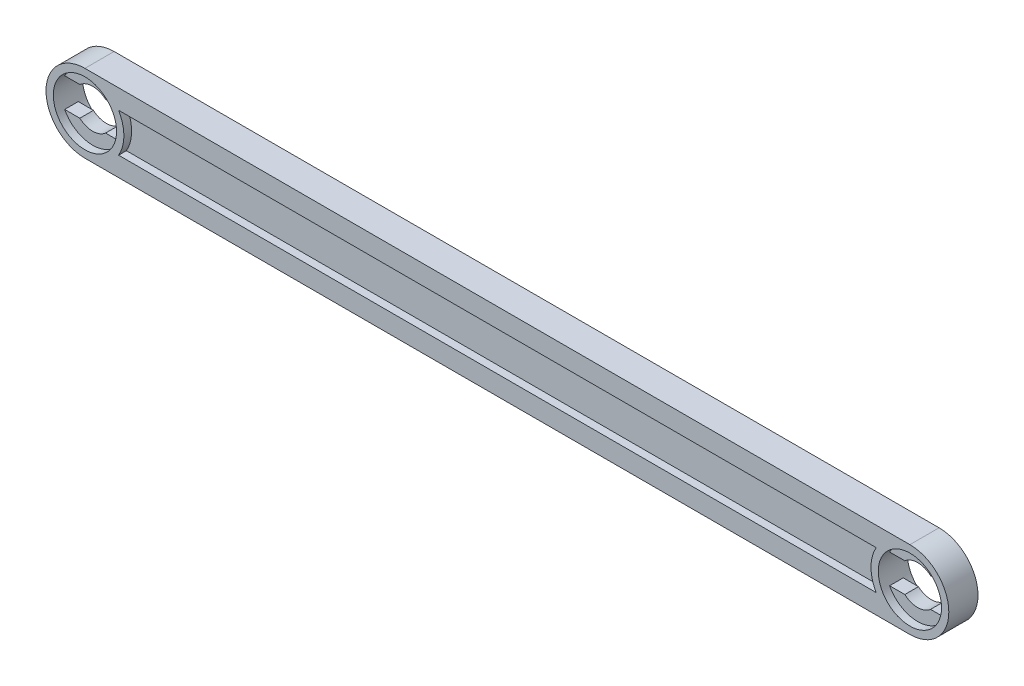
SolidWorks part; units mm, degrees
ref_plane "前视基准面" through (0, 0, 0) normal (0, 0, 1) x (1, 0, 0)
ref_plane "上视基准面" through (0, 0, 0) normal (0, 1, 0) x (1, 0, 0)
ref_plane "右视基准面" through (0, 0, 0) normal (1, 0, 0) x (0, 0, -1)
sketch "草图1" plane through (0, 0, 0) normal (0, 0, 1) x (1, 0, 0)
  line L1 (0, 4) -> (84.8, 4)
  line L3 (0, -4) -> (84.8, -4)
  arc A0 (0, 4) -> (0, -4) centre (0, 0) ccw
  arc A1 (84.8, -4) -> (84.8, 4) centre (84.8, 0) ccw
  dimension "D1" = 84.8
  dimension "D2" = 4
  dimension "D4" = 4
  dimension "D3" = 84.8
extrude "凸台-拉伸1" add sketch "草图1" against normal blind 3
sketch "草图2" plane through (0, 0, 0) normal (0, 0, 1) x (1, 0, 0)
  line L0 (1.3229, -1.5) -> (2.8831, -1.5)
  line L1 (-2.8831, -1.5) -> (-1.3229, -1.5)
  line L2 (1.3229, 1.5) -> (2.8831, 1.5)
  line L3 (-2.8831, 1.5) -> (-1.3229, 1.5)
  arc A0 (1.3229, 1.5) -> (-1.3229, 1.5) centre (0, 0) ccw
  arc A1 (-2.8831, 1.5) -> (-2.8831, -1.5) centre (0, 0) ccw
  arc A3 (2.8831, -1.5) -> (2.8831, 1.5) centre (0, 0) ccw
  arc A4 (-1.3229, -1.5) -> (1.3229, -1.5) centre (0, 0) ccw
extrude "切除-拉伸1" cut sketch "草图2" against normal up to next
sketch "草图3" plane through (0, 0, 0) normal (0, 0, 1) x (1, 0, 0)
  circle A1 centre (0, 0) radius 3.25
extrude "切除-拉伸2" cut sketch "草图3" against normal blind 0.8
extrude "切除-拉伸3" cut sketch "草图3<2>" along normal blind 0.8 from offset 3 offset against normal yes
sketch "草图3<2>" plane through (0, 0, 0) normal (0, 0, 1) x (1, 0, 0) same geometry as "草图3"
pattern_linear "阵列(线性)1" count 2 spacing 84.8 along (1, 0, 0) of "切除-拉伸1", "切除-拉伸2", "切除-拉伸3"
sketch "草图4" plane through (0, 0, 0) normal (0, 0, 1) x (1, 0, 0)
  line L0 (0, 0) -> (0, 2) construction
  line L1 (0, 0) -> (0, -2) construction
  line L2 (0, 2) -> (3.4641, 2) construction
  line L3 (0, -2) -> (3.4641, -2) construction
  line L4 (84.8, 0) -> (84.8, 2) construction
  line L5 (84.8, 2) -> (81.3359, 2) construction
  line L6 (84.8, 0) -> (84.8, -2) construction
  line L7 (84.8, -2) -> (81.3359, -2) construction
  line L8 (3.4641, 2) -> (81.3359, 2)
  line L9 (3.4641, -2) -> (81.3359, -2)
  arc A0 (1.3229, 1.5) -> (-1.3229, 1.5) centre (0, 0) ccw construction
  arc A1 (-1.3229, -1.5) -> (1.3229, -1.5) centre (0, 0) ccw construction
  arc A2 (3.4641, -2) -> (3.4641, 2) centre (0, 0) ccw
  arc A3 (81.3359, 2) -> (81.3359, -2) centre (84.8, 0) ccw
  arc A4 (86.1229, 1.5) -> (83.4771, 1.5) centre (84.8, 0) ccw construction
  arc A5 (83.4771, -1.5) -> (86.1229, -1.5) centre (84.8, 0) ccw construction
extrude "切除-拉伸4" cut sketch "草图4" against normal blind 0.8
sketch "草图5" plane through (0, 0, -3) normal (0, 0, -1) x (-1, 0, 0)
  line L0 (-80.8, -2) -> (-80.8, 2)
  line L1 (-4, -2) -> (-4, 2)
  line L2 (-80.8, 2) -> (-4, 2)
  line L3 (-80.8, 0) -> (-4, 0) construction
  line L4 (-80.8, -2) -> (-4, -2)
  circle A0 centre (-84.8, 0) radius 4 construction
  circle A1 centre (0, 0) radius 4 construction
  dimension "D1" = 2
  dimension "D2" = 2
extrude "切除-拉伸5" cut sketch "草图5" against normal blind 0.8
